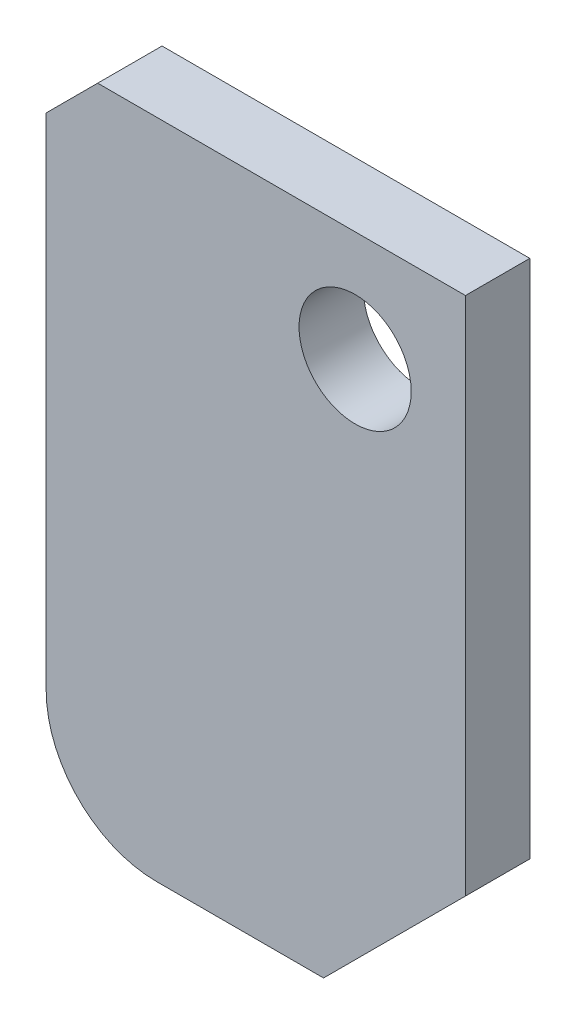
SolidWorks part; units mm, degrees
material "ABS"
ref_plane "前视基准面" through (0, 0, 0) normal (0, 0, 1) x (1, 0, 0)
ref_plane "上视基准面" through (0, 0, 0) normal (0, 1, 0) x (1, 0, 0)
ref_plane "右视基准面" through (0, 0, 0) normal (1, 0, 0) x (0, 0, -1)
other "Configuration Table"
sketch "草图1" plane through (0, 0, 0) normal (0, 0, 1) x (1, 0, 0)
  line L1 (-28.85, -11.75) -> (28.85, -11.75)
  line L2 (-28.85, -11.75) -> (-28.85, 11.75)
  line L3 (-28.85, 11.75) -> (28.85, 11.75)
  line L4 (28.85, -11.75) -> (28.85, 11.75)
  line L5 (-28.85, -11.75) -> (28.85, 11.75) construction
  line L6 (-28.85, 11.75) -> (28.85, -11.75) construction
  point P0 (0, 0)
  dimension "D1" = 57.7
  dimension "D2" = 23.5
extrude "凸台-拉伸1" add sketch "草图1" along normal blind 1.75
sketch "草图2" plane through (0, 0, 1.75) normal (0, 0, 1) x (1, 0, 0)
  line L0 (47.55, 23.2716) -> (47.55, 8.8) construction
  line L1 (30.55, 6.8) -> (27.55, 3.8) construction
  line L2 (45.55, 6.8) -> (30.55, 6.8) construction
  line L3 (27.55, 3.8) -> (27.55, -13.2) construction
  line L4 (47.55, 23.2716) -> (47.55, 8.8) construction
  line L5 (30.55, 6.8) -> (27.55, 3.8) construction
  line L6 (45.55, 6.8) -> (30.55, 6.8) construction
  line L7 (27.55, 3.8) -> (27.55, -13.2) construction
  line L8 (28.85, -11.75) -> (33.85, -11.75)
  line L9 (33.85, -11.75) -> (33.85, 7.8)
  line L10 (33.85, 7.8) -> (41.3921, 7.8)
  line L11 (41.3921, 7.8) -> (45.25, 11.6579)
  line L12 (45.25, 11.6579) -> (45.25, 25.8)
  line L13 (45.25, 25.8) -> (27.25, 25.8)
  line L16 (30.25, 10.8) -> (42.25, 22.8) construction
  line L17 (27.25, 25.8) -> (27.25, 11.75)
  line L18 (28.85, 11.75) -> (-28.85, 11.75) construction
  line L19 (27.25, 11.75) -> (28.85, 11.75)
  line L20 (28.85, 11.75) -> (23.85, -11.75)
  line L21 (-28.85, -11.75) -> (28.85, -11.75) construction
  line L22 (23.85, -11.75) -> (28.85, -11.75)
  arc A0 (45.55, 6.8) -> (47.55, 8.8) centre (45.55, 8.8) ccw construction
  circle A1 centre (42.25, 22.8) radius 1.25 construction
  circle A2 centre (30.25, 10.8) radius 1.25 construction
  arc A3 (45.55, 6.8) -> (47.55, 8.8) centre (45.55, 8.8) ccw construction
  circle A4 centre (42.25, 22.8) radius 1.25 construction
  circle A5 centre (30.25, 10.8) radius 1.25 construction
  circle A6 centre (30.25, 10.8) radius 1.525
  circle A7 centre (42.25, 22.8) radius 1.525
  dimension "D4" = 3.05
  dimension "D1" = 3
  dimension "D2" = 10
  dimension "D3" = 3
  dimension "D5" = 3
  dimension "D6" = 5
  dimension "D7" = 3
  dimension "D8" = 5
extrude "凸台-拉伸2" add sketch "草图2" against normal up to surface (1.75 mm away) up to face at (0, 0, 0)
chamfer "倒角2" distance 8 angle 45 1 edges at (27.25, 25.8, 0.875)
sketch "草图4" plane through (0, 0, 1.75) normal (0, 0, 1) x (1, 0, 0)
  line L0 (27.25, 17.8) -> (24.1216, 14.6716)
  line L1 (24.1216, 14.6716) -> (24.1216, 11.75)
  line L2 (27.25, 11.75) -> (-28.85, 11.75) construction
  line L3 (24.1216, 11.75) -> (27.25, 11.75)
  line L4 (27.25, 11.75) -> (27.25, 17.8)
  line L5 (27.25, 11.75) -> (-28.85, 11.75) construction
  line L6 (35.25, 25.8) -> (27.25, 17.8) construction
  line L7 (27.25, 17.8) -> (27.25, 11.75) construction
extrude "凸台-拉伸3" add sketch "草图4" against normal up to surface (1.75 mm away) up to face at (30.3125, 10.8, 0)
fillet "圆角3" radius 10 1 edges at (24.1216, 11.75, 0.875)
fillet "圆角4" [suppressed] radius 2
fillet "圆角5" radius 3 1 edges at (33.85, 7.8, 0.875)
sketch "草图5" plane through (0, 0, 1.75) normal (0, 0, 1) x (1, 0, 0)
  circle A0 centre (-31.95, -113.7) radius 1.25 construction
  circle A1 centre (-31.95, -95.2) radius 1.25 construction
  circle A2 centre (13.05, -95.2) radius 1.25 construction
  circle A3 centre (13.05, -113.7) radius 1.25 construction
  circle A4 centre (-31.95, -113.7) radius 1.25 construction
  circle A5 centre (-31.95, -95.2) radius 1.25 construction
  circle A6 centre (13.05, -95.2) radius 1.25 construction
  circle A7 centre (13.05, -113.7) radius 1.25 construction
  circle A8 centre (-31.95, -113.7) radius 1.525
  circle A9 centre (-31.95, -95.2) radius 1.525
  circle A10 centre (13.05, -113.7) radius 1.525
  circle A11 centre (13.05, -95.2) radius 1.525
  dimension "D1" = 3.05
extrude "切除-拉伸1" cut sketch "草图5" against normal up to surface (1.75 mm away) rebuild error yes
fillet "圆角6" radius 3 3 edges at (33.85, -11.75, 0.875) (-28.85, -11.75, 0.875) (-28.85, 11.75, 0.875)
sketch "草图6" plane through (0, 0, 1.75) normal (0, 0, 1) x (1, 0, 0)
  line L0 (33.85, 24.4) -> (33.85, 4.8)
  line L1 (35.25, 25.8) -> (24.1216, 14.6716) construction
  line L2 (33.85, 24.4) -> (-29, 24.4)
  line L3 (-29, 24.4) -> (-29, -13)
  line L4 (-29, -13) -> (33.85, -13)
  line L5 (33.85, -13) -> (33.85, 4.8)
  dimension "D1" = 13
  dimension "D2" = 29
extrude "切除-拉伸2" cut sketch "草图6" against normal up to surface (1.75 mm away) up to face at (16.6692, 6.3484, 0)
fillet "圆角7" radius 3 1 edges at (33.85, 4.8, 0.875)
fillet "圆角8" [suppressed] radius 3
sketch "草图7" [suppressed] plane through (0, 0, 0) normal (0, 0, -1) x (-1, 0, 0)
  line L8 (-45.6921, 24.05) -> (-31.85, 24.05)
  line L9 (-49.55, 27.9079) -> (-45.6921, 24.05)
  line L10 (-49.55, 42.05) -> (-49.55, 27.9079)
  line L11 (-26.15, 42.05) -> (-49.55, 42.05)
  line L12 (-26.15, 10) -> (-26.15, 42.05)
  line L13 (-26.15, -13.5) -> (-26.15, 10)
  line L14 (-31.85, -13.5) -> (-26.15, -13.5)
  line L15 (-31.85, 24.05) -> (-31.85, -13.5)
  line L16 (-45.6921, 24.05) -> (-31.85, 24.05)
  line L17 (-49.55, 27.9079) -> (-45.6921, 24.05)
  line L18 (-49.55, 42.05) -> (-49.55, 27.9079)
  line L19 (-26.15, 42.05) -> (-49.55, 42.05)
  line L20 (-26.15, 10) -> (-26.15, 42.05)
  line L21 (-26.15, -13.5) -> (-26.15, 10)
  line L22 (-31.85, -13.5) -> (-26.15, -13.5)
  line L23 (-31.85, 24.05) -> (-31.85, -13.5)
  circle A1 centre (-46.55, 39.05) radius 1.525
  circle A2 centre (-46.55, 39.05) radius 1.525
  circle A3 centre (-34.55, 27.05) radius 1.525
  circle A4 centre (-34.55, 27.05) radius 1.525
  dimension "D1" = 0
  dimension "D2" = 0
  dimension "D3" = 0
sketch "草图8" [suppressed] plane through (0, 0, 0) normal (0, 0, -1) x (-1, 0, 0)
  line L0 (-22.4216, 10) -> (-22.4216, -13.5)
  line L10 (-28.15, -13.5) -> (28.55, -13.5)
  line L11 (-22.4216, 10) -> (-22.4216, 11.0932)
  line L12 (-37.8637, 4.05) -> (-34.15, 4.05)
  line L13 (-41.9642, 7.3221) -> (-39.2779, 4.6358)
  line L14 (-42.55, 20.05) -> (-42.55, 8.7363)
  line L15 (-34.6211, 22.05) -> (-40.55, 22.05)
  line L16 (-23.0074, 12.5074) -> (-31.0855, 20.5855)
  line L18 (28.55, 10) -> (-22.4216, 10)
  line L19 (31.55, -10.5) -> (31.55, 7)
  line L22 (-37.8637, 4.05) -> (-34.15, 4.05)
  line L23 (-41.9642, 7.3221) -> (-39.2779, 4.6358)
  line L24 (-42.55, 20.05) -> (-42.55, 8.7363)
  line L25 (-34.6211, 22.05) -> (-40.55, 22.05)
  line L26 (-23.0074, 12.5074) -> (-31.0855, 20.5855)
  line L30 (28.85, -13.5) -> (-28.85, -13.5) construction
  line L31 (-31.15, -13.5) -> (-22.4216, -13.5)
  line L33 (-28.15, 4.5) -> (-28.15, -13.5)
  line L39 (-31.15, 4.5) -> (-28.15, 4.5)
  line L41 (-31.15, 1.05) -> (-31.15, 4.5)
  line L42 (-31.15, 1.05) -> (-31.15, -13.5)
  line L43 (-22.4216, 10) -> (-22.4216, 11.0932)
  arc A11 (-31.0855, 20.5855) -> (-34.6211, 22.05) centre (-34.6211, 17.05) ccw
  arc A12 (-39.2779, 4.6358) -> (-37.8637, 4.05) centre (-37.8637, 6.05) ccw
  arc A13 (-42.55, 8.7363) -> (-41.9642, 7.3221) centre (-40.55, 8.7363) ccw
  arc A14 (-40.55, 22.05) -> (-42.55, 20.05) centre (-40.55, 20.05) ccw
  arc A15 (-31.0855, 20.5855) -> (-34.6211, 22.05) centre (-34.6211, 17.05) ccw
  arc A16 (-31.15, 1.05) -> (-34.15, 4.05) centre (-34.15, 1.05) ccw
  arc A18 (31.55, 7) -> (28.55, 10) centre (28.55, 7) ccw
  arc A19 (28.55, -13.5) -> (31.55, -10.5) centre (28.55, -10.5) ccw
  arc A22 (-39.2779, 4.6358) -> (-37.8637, 4.05) centre (-37.8637, 6.05) ccw
  arc A23 (-42.55, 8.7363) -> (-41.9642, 7.3221) centre (-40.55, 8.7363) ccw
  arc A24 (-40.55, 22.05) -> (-42.55, 20.05) centre (-40.55, 20.05) ccw
  circle A30 centre (-39.55, 19.05) radius 1.525 construction
  circle A31 centre (-27.55, 7.05) radius 1.525 construction
  circle A32 centre (-39.55, 19.05) radius 1.525
  circle A33 centre (-27.55, 7.05) radius 1.525
  arc A35 (-31.15, 1.05) -> (-34.15, 4.05) centre (-34.15, 1.05) ccw
  arc A37 (-22.4216, 11.0932) -> (-23.0074, 12.5074) centre (-24.4216, 11.0932) ccw
  arc A39 (-22.4216, 11.0932) -> (-23.0074, 12.5074) centre (-24.4216, 11.0932) ccw
  dimension "D1" = 0
extrude "凸台-拉伸5" [suppressed] add sketch "草图8" against normal up to surface (4 mm away)
fillet "圆角10" [suppressed] radius 2
sketch "草图9" [suppressed] plane through (0, 0, 0) normal (0, 0, -1) x (-1, 0, 0)
  circle A0 centre (26.35, 11) radius 1.25 construction
  circle A1 centre (26.35, -11) radius 1.25 construction
  circle A2 centre (-18.65, -11) radius 1.25 construction
  circle A3 centre (-18.65, 11) radius 1.25 construction
  circle A4 centre (26.35, 11) radius 1.25 construction
  circle A5 centre (26.35, -11) radius 1.25 construction
  circle A6 centre (-18.65, -11) radius 1.25 construction
  circle A7 centre (-18.65, 11) radius 1.25 construction
  circle A8 centre (-18.65, 11) radius 1.525
  circle A9 centre (-18.65, -11) radius 1.525
  circle A10 centre (26.35, -11) radius 1.525
  circle A11 centre (26.35, 11) radius 1.525
  dimension "D1" = 3.05
extrude "切除-拉伸3" [suppressed] cut sketch "草图9" against normal up to surface (4 mm away)
sketch "草图11" [suppressed] plane through (0, 0, 0) normal (0, 0, -1) x (-1, 0, 0)
  line L0 (-33.85, -8.75) -> (-33.85, 4.8) construction
  line L1 (-30.85, -11.75) -> (-33.85, -11.75)
  line L2 (-30.85, -11.75) -> (-30.85, 6.25)
  line L3 (-30.85, 6.25) -> (-33.85, 6.25)
  line L4 (-33.85, -11.75) -> (-33.85, 6.25)
  dimension "D1" = 18
extrude "切除-拉伸5" [suppressed] cut sketch "草图11" against normal up to surface (4 mm away)
fillet "圆角11" [suppressed] radius 2
fillet "圆角12" [suppressed] radius 1.2
fillet "圆角14" [suppressed] radius 2
sketch "草图12" [suppressed] plane through (0, 0, 4) normal (0, 0, 1) x (1, 0, 0)
  line L0 (28.85, 13.5) -> (-26.85, 13.5) construction
  line L1 (-23.35, -8.5) -> (15.65, -8.5)
  line L2 (-23.35, -8.5) -> (-23.35, 8.5)
  line L3 (-23.35, 8.5) -> (15.65, 8.5)
  line L4 (15.65, -8.5) -> (15.65, 8.5)
  line L5 (-23.35, -8.5) -> (15.65, 8.5) construction
  line L6 (-23.35, 8.5) -> (15.65, -8.5) construction
  line L7 (-26.85, -13.5) -> (28.85, -13.5) construction
  circle A0 centre (18.65, 11) radius 1.525 construction
  circle A1 centre (-26.35, 11) radius 1.525 construction
  point P0 (-3.85, 0)
  dimension "D1" = 3
  dimension "D2" = 3
  dimension "D3" = 5
  dimension "D4" = 5
extrude "切除-拉伸6" [suppressed] cut sketch "草图12" against normal up to surface (4 mm away)
fillet "圆角15" [suppressed] radius 2
sketch "草图13" [suppressed] plane through (0, 0, 0) normal (0, 0, -1) x (-1, 0, 0)
  line L0 (-24.1216, 11.75) -> (25.85, 11.75) construction
  line L1 (-18.35, -6.75) -> (20.65, -6.75)
  line L2 (-18.35, -6.75) -> (-18.35, 6.75)
  line L3 (-18.35, 6.75) -> (20.65, 6.75)
  line L4 (20.65, -6.75) -> (20.65, 6.75)
  line L5 (-18.35, -6.75) -> (20.65, 6.75) construction
  line L6 (-18.35, 6.75) -> (20.65, -6.75) construction
  line L7 (25.85, -11.75) -> (-30.85, -11.75) construction
  circle A0 centre (23.65, 9.25) radius 1.525 construction
  circle A1 centre (-21.35, 9.25) radius 1.525 construction
  point P0 (1.15, 0)
  dimension "D1" = 3
  dimension "D2" = 3
  dimension "D3" = 5
  dimension "D4" = 5
extrude "切除-拉伸7" [suppressed] cut sketch "草图13" against normal up to surface (4 mm away)
fillet "圆角16" [suppressed] radius 2
sketch "草图14" [suppressed] plane through (0, 0, 4) normal (0, 0, 1) x (1, 0, 0)
  line L1 (30.85, 5.05) -> (36.85, 5.05)
  line L2 (30.85, 5.05) -> (30.85, 2.8)
  line L3 (30.85, 2.8) -> (36.85, 2.8)
  line L4 (36.85, 5.05) -> (36.85, 2.8)
extrude "切除-拉伸8" [suppressed] cut sketch "草图14" against normal up to surface (4 mm away)
fillet "圆角19" [suppressed] radius 5
fillet "圆角20" [suppressed] radius 5
sketch "草图17" [suppressed] plane through (0, 0, 0) normal (0, 0, -1) x (-1, 0, 0)
  line L0 (25.85, -11.75) -> (-30.85, -11.75) construction
  line L1 (-27.55, -11.75) -> (-35.85, -11.75)
  line L2 (-27.55, -11.75) -> (-27.55, 2.8)
  line L3 (-27.55, 2.8) -> (-35.85, 2.8)
  line L4 (-35.85, -11.75) -> (-35.85, 2.8)
  line L5 (-30.85, -11.75) -> (-30.85, 4.398) construction
  line L6 (-36.85, 2.8) -> (-40.5637, 2.8) construction
  arc A0 (-30.85, 7.8) -> (-35.85, 12.8) centre (-35.85, 7.8) ccw construction
  dimension "D1" = 3.3
extrude "切除-拉伸9" [suppressed] cut sketch "草图17" against normal up to surface (4 mm away)
sketch "草图18" [suppressed] plane through (0, 0, 4) normal (0, 0, 1) x (1, 0, 0)
  line L0 (27.55, 3.8) -> (27.55, -13.2) construction
  line L1 (27.55, 6.8) -> (27.55, -13.2)
  line L2 (45.55, 6.8) -> (30.55, 6.8) construction
  line L3 (45.55, 6.8) -> (27.55, 6.8)
  line L4 (45.55, 6.8) -> (45.55, -13.2)
  line L5 (45.55, -13.2) -> (27.55, -13.2)
extrude "切除-拉伸10" [suppressed] cut sketch "草图18" against normal blind 50
sketch "草图19" [suppressed] plane through (0, 0, 0) normal (0, 0, -1) x (-1, 0, 0)
  line L0 (-41.9779, 8.3858) -> (-40.3921, 6.8)
  line L1 (-40.3921, 6.8) -> (-34.6139, 6.8)
  line L2 (-41.9779, 8.3858) -> (-44.6642, 11.0721) construction
  line L3 (-41.9779, 8.3858) -> (-34.6139, 8.3858)
  line L4 (-34.6139, 8.3858) -> (-34.6139, 6.8)
extrude "凸台-拉伸6" [suppressed] add sketch "草图19" against normal up to surface (4 mm away)
sketch "草图20" [suppressed] plane through (0, 0, 0) normal (0, 0, -1) x (-1, 0, 0)
  circle A0 centre (-30.25, 10.8) radius 1.525
  dimension "D1" = 3.05
extrude "切除-拉伸11" [suppressed] cut sketch "草图20" against normal up to surface (4 mm away)
sketch "草图21" [suppressed] plane through (0, 0, 0) normal (0, 0, -1) x (-1, 0, 0)
  line L0 (-34.6057, 24.9984) -> (-14.1216, 11.75)
  line L1 (-24.1216, 11.75) -> (25.85, 11.75) construction
  line L2 (-14.1216, 11.75) -> (-24.1216, 11.75)
  line L3 (-24.1216, 11.75) -> (-34.6057, 24.9984)
  arc A0 (-33.7855, 24.3355) -> (-37.3211, 25.8) centre (-37.3211, 20.8) ccw construction
  dimension "D1" = 10
extrude "凸台-拉伸7" [suppressed] add sketch "草图21" against normal up to surface (4 mm away)
fillet "圆角21" [suppressed] radius 10
fillet "圆角22" [suppressed] radius 2
fillet "圆角23" [suppressed] radius 2
fillet "圆角24" [suppressed] radius 2
sketch "草图22" [suppressed] plane through (0, 0, 0) normal (0, 0, -1) x (-1, 0, 0)
  line L0 (-24.85, 2.05) -> (-24.85, -14.95) construction
  line L1 (-25.7287, 10.9287) -> (-38.9713, 24.1713) construction
  line L2 (-27.85, 5.05) -> (-42.85, 5.05) construction
  line L3 (-24.85, 5.05) -> (-24.85, -13.5)
  line L4 (-21.85, 7.05) -> (-38.9713, 24.1713)
  line L5 (-24.85, 5.05) -> (-42.85, 5.05)
  line L6 (-38.9713, 24.1713) -> (-42.85, 24.1713)
  line L7 (-42.85, 24.1713) -> (-42.85, 5.05)
  line L8 (26.85, -13.5) -> (-28.85, -13.5) construction
  line L9 (-21.85, 7.05) -> (-21.85, -13.5)
  line L10 (-21.85, -13.5) -> (-24.85, -13.5)
  circle A0 centre (-27.55, 9.05) radius 1.25 construction
  circle A1 centre (-39.55, 21.05) radius 1.525 construction
  circle A2 centre (-27.55, 9.05) radius 1.25
  circle A3 centre (-39.55, 21.05) radius 1.525
  dimension "D1" = 3
extrude "凸台-拉伸8" [suppressed] add sketch "草图22" against normal up to surface (4 mm away)
sketch "草图23" [suppressed] plane through (0, 0, 0) normal (0, 0, -1) x (-1, 0, 0)
  line L1 (-24.85, -13.5) -> (-28.85, -13.5)
  line L2 (-24.85, -13.5) -> (-24.85, 5.05)
  line L3 (-24.85, 5.05) -> (-28.85, 5.05)
  line L4 (-28.85, -13.5) -> (-28.85, 5.05)
  circle A0 centre (-27.55, 9.05) radius 1.25 construction
  circle A1 centre (-27.55, 9.05) radius 1.25
extrude "切除-拉伸12" [suppressed] cut sketch "草图23" against normal up to surface (4 mm away)
sketch "草图24" [suppressed] plane through (0, 0, 0) normal (0, 0, -1) x (-1, 0, 0)
  line L0 (-38.9713, 24.1713) -> (-18.3, 13.5)
  line L1 (-28.3, 13.5) -> (26.85, 13.5) construction
  line L2 (-18.3, 13.5) -> (-28.3, 13.5)
  line L3 (-28.3, 13.5) -> (-38.9713, 24.1713)
  dimension "D1" = 10
extrude "凸台-拉伸9" [suppressed] add sketch "草图24" against normal up to surface (4 mm away)
fillet "圆角25" [suppressed] radius 2
fillet "圆角26" [suppressed] radius 10
equation "\"D4@草图12\"=\"D3@草图12\""
